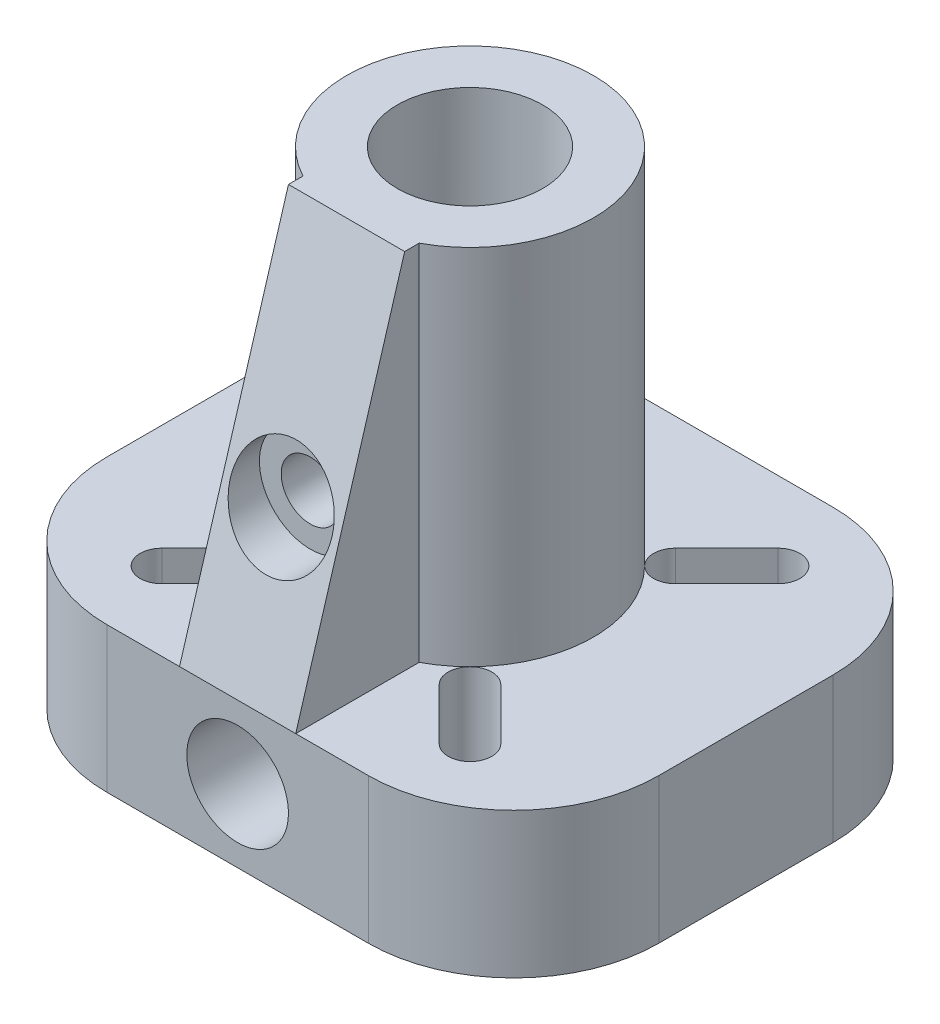
SolidWorks part; units mm, degrees
ref_plane "前视基准面" through (0, 0, 0) normal (0, 0, 1) x (1, 0, 0)
ref_plane "上视基准面" through (0, 0, 0) normal (0, 1, 0) x (1, 0, 0)
ref_plane "右视基准面" through (0, 0, 0) normal (1, 0, 0) x (0, 0, -1)
sketch "草图1" plane through (0, 0, 0) normal (0, 1, 0) x (1, 0, 0)
  line L0 (0, 0) -> (19, 0)
  line L1 (0, 0) -> (-19, 0)
  line L2 (-19, 0) -> (-19, 64)
  line L3 (19, 0) -> (19, 64)
  line L6 (10.6066, 19.9292) -> (10.6066, 16.885)
  line L7 (-7.0711, 47.0711) -> (-10.6066, 50.6066) construction
  line L8 (-8.1317, 46.0104) -> (-11.6673, 49.5459)
  line L9 (-6.0104, 48.1317) -> (-9.5459, 51.6673)
  line L10 (7.0711, 47.0711) -> (10.6066, 50.6066) construction
  line L11 (6.0104, 48.1317) -> (9.5459, 51.6673)
  line L12 (8.1317, 46.0104) -> (11.6673, 49.5459)
  line L13 (7.0711, 32.9289) -> (10.6066, 29.3934) construction
  line L14 (8.1317, 33.9896) -> (11.6673, 30.4541)
  line L15 (6.0104, 31.8683) -> (9.5459, 28.3327)
  line L16 (-7.0711, 32.9289) -> (-10.6066, 29.3934) construction
  line L17 (-6.0104, 31.8683) -> (-9.5459, 28.3327)
  line L18 (-8.1317, 33.9896) -> (-11.6673, 30.4541)
  line L19 (-10.6066, 60.0708) -> (-10.6066, 63.115)
  line L20 (10.6066, 60.0708) -> (10.6066, 63.115)
  line L21 (-10.6066, 19.9292) -> (-10.6066, 16.885)
  arc A0 (-19, 64) -> (19, 64) centre (0, 0) cw
  circle A1 centre (0, 40) radius 5
  arc A2 (-8.1317, 46.0104) -> (-6.0104, 48.1317) centre (-7.0711, 47.0711) ccw
  arc A3 (-9.5459, 51.6673) -> (-11.6673, 49.5459) centre (-10.6066, 50.6066) ccw
  arc A4 (6.0104, 48.1317) -> (8.1317, 46.0104) centre (7.0711, 47.0711) ccw
  arc A5 (11.6673, 49.5459) -> (9.5459, 51.6673) centre (10.6066, 50.6066) ccw
  arc A6 (8.1317, 33.9896) -> (6.0104, 31.8683) centre (7.0711, 32.9289) ccw
  arc A7 (9.5459, 28.3327) -> (11.6673, 30.4541) centre (10.6066, 29.3934) ccw
  arc A8 (-6.0104, 31.8683) -> (-8.1317, 33.9896) centre (-7.0711, 32.9289) ccw
  arc A9 (-11.6673, 30.4541) -> (-9.5459, 28.3327) centre (-10.6066, 29.3934) ccw
  arc A12 (10.6066, 63.115) -> (-10.6066, 63.115) centre (0, 0) ccw
  arc A13 (10.6066, 60.0708) -> (-10.6066, 60.0708) centre (0, 0) ccw
  arc A14 (10.6066, 19.9292) -> (-10.6066, 19.9292) centre (0, 80) cw
  arc A15 (10.6066, 16.885) -> (-10.6066, 16.885) centre (0, 80) cw
  circle A16 centre (-16.1716, 2.8284) radius 1.5
  circle A17 centre (-16.1716, 61.1716) radius 1.5
  circle A18 centre (16.1716, 61.1716) radius 1.5
  circle A19 centre (16.1716, 2.8284) radius 1.5
  point P9 (-8.8388, 48.8388)
  point P19 (8.8388, 48.8388)
  point P26 (8.8388, 31.1612)
  point P33 (-8.8388, 31.1612)
  point P40 (0, 40)
extrude "凸台-拉伸2" add sketch "草图1" along normal blind 3
sketch "草图2" plane through (0, 3, 0) normal (0, 1, 0) x (1, 0, 0)
  line L0 (0, 40) -> (0, 24)
  line L3 (-19, 64) -> (-19, 0) construction
  line L4 (-19, 24) -> (19, 24)
  line L5 (19, 0) -> (19, 64) construction
  line L6 (-19, 24) -> (30.8391, 24)
  line L7 (-19, 24) -> (-19, -5.12)
  line L8 (-19, -5.12) -> (30.8391, -5.12)
  line L9 (30.8391, 24) -> (30.8391, -5.12)
  line M14 (-19, 0) -> (19, 0)
  line M15 (19, 0) -> (19, 64)
  line M17 (-19, 64) -> (-19, 0)
  circle M18 centre (-16.1716, 2.8284) radius 1.5
  arc M28 (-10.6066, 19.9292) -> (10.6066, 19.9292) centre (0, 80) ccw
  line M29 (10.6066, 19.9292) -> (10.6066, 16.885)
  arc M30 (10.6066, 16.885) -> (-10.6066, 16.885) centre (0, 80) cw
  line M31 (-10.6066, 16.885) -> (-10.6066, 19.9292)
  circle M34 centre (16.1716, 2.8284) radius 1.5
extrude "切除-拉伸1" cut sketch "草图2" against normal blind 37 contours L4 M17 M14 M15 M18 M31 M28 M29 M30 M34 region at (0, 3, -11.7105)
sketch "草图3" plane through (0, 0, 0) normal (0, -1, 0) x (1, 0, 0)
  line L0 (-19, -64) -> (-19, -24) construction
  line L1 (19, -64) -> (-19, -64)
  line L2 (19, -64) -> (19, -57.2623)
  line L3 (19, -57.2623) -> (-19, -57.2623)
  line L4 (-19, -64) -> (-19, -57.2623)
extrude "凸台-拉伸3" add sketch "草图3" against normal blind 3
sketch "草图5" plane through (0, 3, 0) normal (0, 1, 0) x (1, 0, 0)
  line L1 (-19, 64) -> (34.6033, 64)
  line L2 (-19, 64) -> (-19, 83.817)
  line L3 (-19, 83.817) -> (34.6033, 83.817)
  line L4 (34.6033, 64) -> (34.6033, 83.817)
extrude "切除-拉伸2" cut sketch "草图5" against normal blind 3
sketch "草图6" plane through (0, 3, 0) normal (0, 1, 0) x (1, 0, 0)
  line L1 (-19, 64) -> (19, 64)
  line L2 (-19, 64) -> (-19, 24)
  line L3 (-19, 24) -> (19, 24)
  line L4 (19, 64) -> (19, 24)
extrude "凸台-拉伸5" add sketch "草图6" along normal blind 7
sketch "草图8" plane through (0, 0, 0) normal (0, -1, 0) x (-1, 0, 0)
  line L1 (-19, 56) -> (19, 56)
  line L2 (-19, 56) -> (-19, 24)
  line L3 (-19, 24) -> (19, 24)
  line L4 (19, 56) -> (19, 24)
  line L5 (-19, 56) -> (19, 24) construction
  line L6 (-19, 24) -> (19, 56) construction
  line L7 (57, 72) -> (-19, 72)
  line L8 (57, 72) -> (57, 56)
  line L9 (57, 56) -> (-19, 56)
  line L10 (-19, 72) -> (-19, 56)
  line L11 (57, 72) -> (-19, 56) construction
  line L12 (57, 56) -> (-19, 72) construction
  point P0 (0, 40)
  point P7 (19, 64)
  line M1 (19, 64) -> (-19, 64)
  line M2 (-19, 64) -> (-19, 24)
  line M4 (19, 24) -> (19, 64)
extrude "切除-拉伸4" cut sketch "草图8" against normal blind 44 contours L1 M2 M4 M1 region at (0, 0, -60)
sketch "草图9" plane through (0, 0, 0) normal (0, -1, 0) x (1, 0, 0)
  circle A0 centre (0, -40) radius 5
extrude "切除-拉伸5" cut sketch "草图9" against normal blind 44
sketch "草图11" plane through (0, 0, 0) normal (0, -1, 0) x (1, 0, 0)
  line L0 (10.6066, -29.3934) -> (7.0711, -32.9289) construction
  line L1 (11.6673, -30.4541) -> (8.1317, -33.9896)
  line L2 (9.5459, -28.3327) -> (6.0104, -31.8683)
  line L3 (10.6066, -50.6066) -> (7.0711, -47.0711) construction
  line L4 (9.5459, -51.6673) -> (6.0104, -48.1317)
  line L5 (11.6673, -49.5459) -> (8.1317, -46.0104)
  line L6 (-10.6066, -50.6066) -> (-7.0711, -47.0711) construction
  line L7 (-11.6673, -49.5459) -> (-8.1317, -46.0104)
  line L8 (-9.5459, -51.6673) -> (-6.0104, -48.1317)
  line L9 (-10.6066, -29.3934) -> (-7.0711, -32.9289) construction
  line L10 (-9.5459, -28.3327) -> (-6.0104, -31.8683)
  line L11 (-11.6673, -30.4541) -> (-8.1317, -33.9896)
  arc A0 (11.6673, -30.4541) -> (9.5459, -28.3327) centre (10.6066, -29.3934) ccw
  arc A1 (6.0104, -31.8683) -> (8.1317, -33.9896) centre (7.0711, -32.9289) ccw
  arc A3 (9.5459, -51.6673) -> (11.6673, -49.5459) centre (10.6066, -50.6066) ccw
  arc A4 (8.1317, -46.0104) -> (6.0104, -48.1317) centre (7.0711, -47.0711) ccw
  arc A5 (-11.6673, -49.5459) -> (-9.5459, -51.6673) centre (-10.6066, -50.6066) ccw
  arc A6 (-6.0104, -48.1317) -> (-8.1317, -46.0104) centre (-7.0711, -47.0711) ccw
  arc A7 (-9.5459, -28.3327) -> (-11.6673, -30.4541) centre (-10.6066, -29.3934) ccw
  arc A8 (-8.1317, -33.9896) -> (-6.0104, -31.8683) centre (-7.0711, -32.9289) ccw
  point P4 (8.8388, -31.1612)
  point P16 (8.8388, -48.8388)
  point P23 (-8.8388, -48.8388)
  point P30 (-8.8388, -31.1612)
  point P35 (0, -40)
  dimension "D1" = 4
extrude "切除-拉伸6" cut sketch "草图11" against normal blind 44
sketch "草图13" plane through (0, 10, 0) normal (0, 1, 0) x (1, 0, 0)
  circle A0 centre (0, 40) radius 8.5
extrude "凸台-拉伸6" add sketch "草图13" along normal blind 25
sketch "草图14" plane through (0, 35, 0) normal (0, 1, 0) x (1, 0, 0)
  circle A0 centre (0, 40) radius 3
extrude "切除-拉伸7" cut sketch "草图14" against normal blind 25
sketch "草图15" plane through (0, 0, 0) normal (1, 0, 0) x (0, 0, -1)
  line L0 (31.5, 35) -> (24, 10)
  line L1 (24, 10) -> (31.5, 10)
  line L2 (31.5, 35) -> (32.9286, 35)
  line L3 (48.5, 35) -> (31.5, 35) construction
  line L4 (32.9286, 35) -> (32.9286, 10)
  line L5 (24, 10) -> (56, 10) construction
  line L6 (32.9286, 10) -> (31.5, 10)
extrude "凸台-拉伸7" add sketch "草图15" along normal mid plane 8
fillet "圆角1" radius 10 4 edges at (19, 5, -24) (-19, 5, -24) (19, 5, -56) (-19, 5, -56)
sketch "草图16" plane through (0, 0, 0) normal (0, -1, 0) x (1, 0, 0)
  circle A0 centre (0, -40) radius 5
extrude "切除-拉伸8" cut sketch "草图16" against normal blind 598
sketch "草图17" plane through (0, 0, 0) normal (0, -1, 0) x (1, 0, 0)
  circle A0 centre (5, -40) radius 2
  circle A1 centre (0, -40) radius 5 construction
  circle A2 centre (0, -45) radius 2
  circle A3 centre (-5, -40) radius 2
  circle A4 centre (0, -35) radius 2
  point P13 (0, -40)
  dimension "D1" = 4
extrude "切除-拉伸9" cut sketch "草图17" against normal blind 5
sketch "草图18" plane through (0, 0, -24) normal (0, 0, 1) x (1, 0, 0)
  line L0 (0, 0) -> (0, 10)
  line L1 (9, 0) -> (-9, 0) construction
  line L2 (4, 10) -> (-4, 10) construction
  circle A0 centre (0, 5) radius 2
extrude "切除-拉伸10" cut sketch "草图18" against normal blind 35 contours L0 A0 | L0 A0 region at (-0.8488, 5, -24) region at (0.8488, 5, -24)
sketch "草图19" plane through (0, 0, -24) normal (0, 0, 1) x (1, 0, 0)
  circle A0 centre (0, 5) radius 3.5
extrude "切除-拉伸11" cut sketch "草图19" against normal blind 5
sketch "草图20" plane through (0, 0, -24) normal (0, 0, 1) x (1, 0, 0)
  line L0 (0, 5) -> (0, 35)
  line L3 (4, 35) -> (-4, 35) construction
  circle A0 centre (0, 20) radius 2
extrude "切除-拉伸12" cut sketch "草图20" against normal blind 32 contours L0 A0 | L0 A0 region at (-0.8488, 20, -24) region at (0.8488, 20, -24)
sketch "草图21" plane through (0, 0, -24) normal (0, 0, 1) x (1, 0, 0)
  circle A0 centre (0, 20) radius 3.5
extrude "切除-拉伸13" cut sketch "草图21" against normal blind 5
